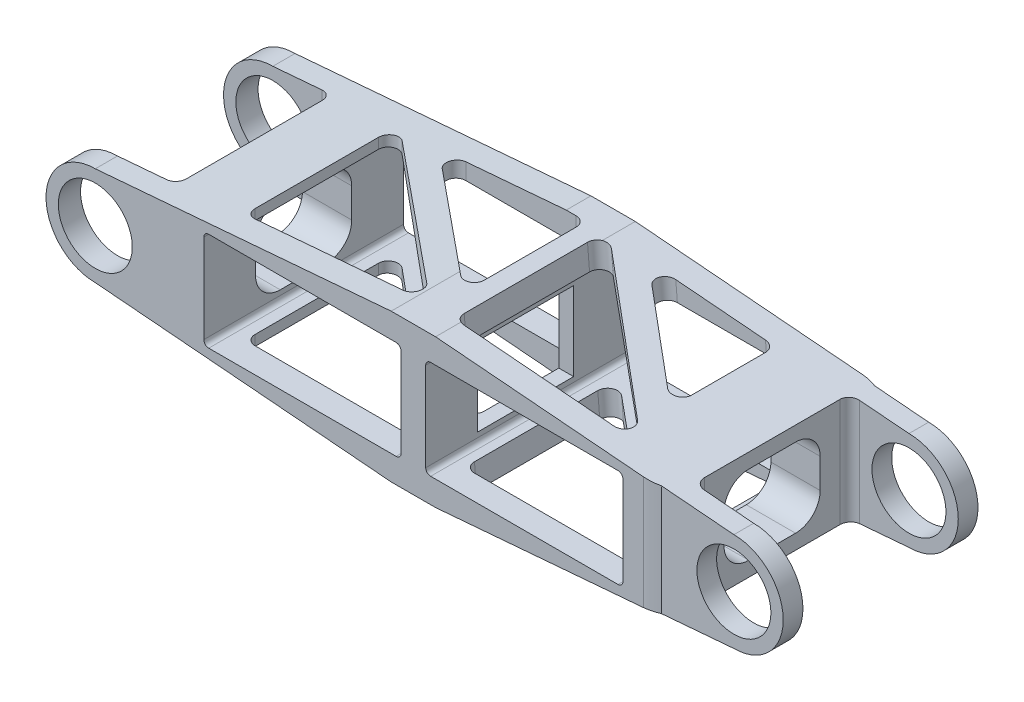
SolidWorks part; units mm, degrees
ref_plane "Plan de face" through (0, 0, 0) normal (0, 0, 1) x (1, 0, 0)
ref_plane "Plan de dessus" through (0, 0, 0) normal (0, 1, 0) x (1, 0, 0)
ref_plane "Plan de droite" through (0, 0, 0) normal (1, 0, 0) x (0, 0, -1)
sketch "Esquisse1" plane through (0, 0, 0) normal (0, 0, 1) x (1, 0, 0)
  line L1 (0, 0) -> (150, 0)
  line L2 (0, 0) -> (0, 30)
  line L3 (0, 30) -> (150, 30)
  line L4 (150, 0) -> (150, 30)
  dimension "D1" = 30
  dimension "D2" = 150
extrude "Boss.-Extru.1" add sketch "Esquisse1" along normal blind 40.5
sketch "Esquisse3" plane through (0, 0, 40.5) normal (0, 0, 1) x (1, 0, 0)
  line L0 (150, 0) -> (150, 30) construction
  arc A0 (150, 0) -> (150, 30) centre (150, 15) ccw
  circle A1 centre (150, 15) radius 7.5
  line M3 (150, 0) -> (150, 30)
  dimension "D1" = 15
extrude "Boss.-Extru.2" add sketch "Esquisse3" against normal through all contours A1 A0 M3 region at (150.3354, 3.75, 40.5)
extrude "Enlèv. mat.-Extru.2" cut sketch "Esquisse3<3>" against normal through all contours A1 M3 region at (146.8169, 15, 40.5)
sketch "Esquisse3<3>" plane through (0, 0, 40.5) normal (0, 0, 1) x (1, 0, 0) same geometry as "Esquisse3"
sketch "Esquisse4" plane through (0, 0, 0) normal (-1, 0, 0) x (0, 0, 1)
  line L0 (0, 30) -> (0, 0) construction
  line L1 (4.5, -6.4053) -> (36, -6.4053)
  line L2 (4.5, -6.4053) -> (4.5, 38.4976)
  line L3 (4.5, 38.4976) -> (36, 38.4976)
  line L4 (36, -6.4053) -> (36, 38.4976)
  line L5 (40.5, 30) -> (40.5, 0) construction
  dimension "D1" = 4.5
  dimension "D2" = 4.5
extrude "Enlèv. mat.-Extru.3" cut sketch "Esquisse4" against normal blind 50 from offset 138 offset against normal yes
sketch "Esquisse5" plane through (0, 0, 0) normal (0, 0, -1) x (-1, 0, 0)
  line L0 (-150, 5) -> (-90, 0)
  line L1 (0, 0) -> (-150, 0) construction
  line L2 (-90, 0) -> (-97.1695, -29.0949)
  line L3 (-97.1695, -29.0949) -> (-150.8097, -33.3502)
  line L4 (-150.8097, -33.3502) -> (-184.8879, -24.3272)
  line L5 (-184.8879, -24.3272) -> (-184.8879, 20.3818)
  line L6 (-184.8879, 20.3818) -> (-179.0278, 90.7023)
  line L7 (-179.0278, 90.7023) -> (-113.2138, 74.2307)
  line L8 (-113.2138, 74.2307) -> (-110.8934, 74.2182)
  line L9 (-80.3627, 70.0357) -> (-78.45, 69.7746)
  line L10 (-110.8934, 74.2182) -> (-88.7692, 44.7696)
  line L11 (-88.7692, 44.7696) -> (-90, 30)
  line L12 (-150, 30) -> (0, 30) construction
  line L13 (-90, 30) -> (-150, 25)
  arc A0 (-150, 25) -> (-150, 5) centre (-150, 15) ccw
  line M2 (0, 30) -> (-150, 30)
  arc M3 (-150, 30) -> (-150, 0) centre (-150, 15) ccw
  line M4 (-150, 0) -> (0, 0)
  dimension "D1" = 20
  dimension "D2" = 60
  dimension "D3" = 60
extrude "Enlèv. mat.-Extru.4" cut sketch "Esquisse5" against normal blind 50 contours A0 L13 L0 M2 M3 M4 region at (120.0671, 1.695, 0)
sketch "Esquisse6" plane through (0, 0, 0) normal (0, 0, -1) x (-1, 0, 0)
  line L1 (-179.8706, 2.3854) -> (-139.062, 2.3854)
  line L2 (-179.8706, 2.3854) -> (-179.8706, 33.5977)
  line L3 (-179.8706, 33.5977) -> (-139.062, 33.5977)
  line L4 (-139.062, 2.3854) -> (-139.062, 33.5977)
extrude "Enlèv. mat.-Extru.5" cut sketch "Esquisse6" against normal blind 0.5
sketch "Esquisse7" plane through (0, 0, 40.5) normal (0, 0, 1) x (1, 0, 0)
  line L1 (165.9667, 35.4579) -> (135.2799, 35.4579)
  line L2 (165.9667, 35.4579) -> (165.9667, -12.2047)
  line L3 (165.9667, -12.2047) -> (135.2799, -12.2047)
  line L4 (135.2799, 35.4579) -> (135.2799, -12.2047)
extrude "Enlèv. mat.-Extru.6" cut sketch "Esquisse7" against normal blind 0.5
sketch "Esquisse8" plane through (0, 0, 0) normal (0, 0, -1) x (-1, 0, 0)
  line L0 (0, 15) -> (-256, 15) construction
  line L1 (-127, 5) -> (-89, 5)
  line L2 (-128, 6) -> (-128, 24)
  line L3 (-127, 25) -> (-89, 25)
  line L4 (-88, 6) -> (-88, 24)
  line L5 (0, 30) -> (0, 0) construction
  arc A0 (-89, 25) -> (-88, 24) centre (-89, 24) cw
  arc A1 (-88, 6) -> (-89, 5) centre (-89, 6) cw
  arc A2 (-127, 25) -> (-128, 24) centre (-127, 24) ccw
  arc A3 (-128, 6) -> (-127, 5) centre (-127, 6) ccw
  circle A4 centre (-150, 15) radius 7.5 construction
  point P8 (-128, 15)
  point P13 (-88, 5)
  point P16 (-128, 25)
  point P19 (-128, 5)
  dimension "D3" = 1
  dimension "D1" = 20
  dimension "D2" = 40
  dimension "D4" = 22
extrude "Enlèv. mat.-Extru.7" cut sketch "Esquisse8" against normal through all
fillet "Congé1" radius 2 2 edges at (138, 15, 4.5) (138, 15, 36)
fillet "Congé2" radius 10 2 edges at (139.062, 15, 0) (135.2799, 15, 40.5)
sketch "Esquisse9" plane through (138, 0, 0) normal (1, 0, 0) x (0, 0, -1)
  line L0 (-6.5, 26) -> (-34, 26) construction
  line L1 (-10.5, 23) -> (-30, 23)
  line L2 (-10.5, 23) -> (-10.5, 7)
  line L3 (-10.5, 7) -> (-30, 7)
  line L4 (-30, 23) -> (-30, 7)
  line L5 (-6.5, 15) -> (-14.5, 15) construction
  line L6 (-6.5, 4) -> (-6.5, 26) construction
  line L7 (-20.25, 41.5871) -> (-20.25, 4.4129) construction
  point P8 (-10.5, 15)
  point P13 (-20.25, 23)
  dimension "D1" = 3
  dimension "D2" = 13.75
  dimension "D3" = 4
extrude "Enlèv. mat.-Extru.8" cut sketch "Esquisse9" against normal through all
sketch "Esquisse10" plane through (0.6207, -7.4483, 0) normal (0.083, -0.9965, 0) x (0.9965, 0.083, 0)
  line L0 (121.974, 23.5364) -> (103.974, 8.5364)
  line L1 (105.2543, 5) -> (123.2543, 5)
  line L2 (125.2543, 7) -> (125.2543, 22)
  line L3 (124.2763, 31.9636) -> (94.2763, 6.9636)
  line L4 (90.9959, 8.5) -> (90.9959, 33.5)
  line L5 (92.9959, 35.5) -> (122.9959, 35.5)
  line L6 (131.9926, 40.5) -> (89.6891, 40.5) construction
  line L8 (135.7879, 0) -> (89.6891, 0) construction
  arc A0 (94.2763, 6.9636) -> (90.9959, 8.5) centre (92.9959, 8.5) cw
  arc A1 (90.9959, 33.5) -> (92.9959, 35.5) centre (92.9959, 33.5) cw
  arc A2 (122.9959, 35.5) -> (124.2763, 31.9636) centre (122.9959, 33.5) cw
  arc A3 (105.2543, 5) -> (103.974, 8.5364) centre (105.2543, 7) cw
  arc A4 (125.2543, 22) -> (121.974, 23.5364) centre (123.2543, 22) ccw
  arc A5 (125.2543, 7) -> (123.2543, 5) centre (123.2543, 7) cw
  point P15 (0, 0)
  point P16 (125.5669, 26.3)
  point P17 (125.1675, 26.3)
  dimension "D1" = 2
  dimension "D7" = 2
  dimension "D2" = 30
  dimension "D3" = 25
  dimension "D4" = 5
  dimension "D5" = 5
  dimension "D6" = 5
  dimension "D8" = 15
extrude "Enlèv. mat.-Extru.9" cut sketch "Esquisse10" against normal through all
fillet "Congé4" radius 5 4 edges at (133, 7, 30) (133, 7, 10.5) (133, 23, 10.5) (133, 23, 30)
sketch "Esquisse11" plane through (0, 0, 0) normal (0, 0, -1) x (-1, 0, 0)
  line L0 (-88, 15) -> (-78, 15) construction
  line L1 (-82, 5) -> (-44, 5)
  line L2 (-83, 6) -> (-83, 24)
  line L3 (-82, 25) -> (-44, 25)
  line L4 (-43, 6) -> (-43, 24)
  line L5 (-88, 6) -> (-88, 24) construction
  arc A0 (-83, 24) -> (-82, 25) centre (-82, 24) cw
  arc A1 (-44, 25) -> (-43, 24) centre (-44, 24) cw
  arc A2 (-43, 6) -> (-44, 5) centre (-44, 6) cw
  arc A3 (-82, 5) -> (-83, 6) centre (-82, 6) cw
  point P8 (-83, 15)
  point P11 (-83, 25)
  point P16 (-43, 5)
  point P19 (-83, 5)
  dimension "D3" = 1
  dimension "D1" = 20
  dimension "D2" = 40
  dimension "D4" = 5
extrude "Enlèv. mat.-Extru.10" cut sketch "Esquisse11" against normal through all and the other way through all
sketch "Esquisse12" plane through (0, 0, 0) normal (0, -1, 0) x (1, 0, 0)
  line L0 (81.7501, 27.1653) -> (59.3561, 8.5036)
  line L1 (60.6245, 5) -> (83.0186, 5)
  line L2 (85, 6.9814) -> (85, 25.6431)
  line L3 (79.5697, 31.8568) -> (49.5697, 6.8568)
  line L4 (46.2893, 8.3932) -> (46.2893, 33.3932)
  line L5 (48.2893, 35.3932) -> (78.2893, 35.3932)
  line L6 (0, 0) -> (90, 0) construction
  line L7 (90, 40.5) -> (90, 0) construction
  arc A0 (49.5697, 6.8568) -> (46.2893, 8.3932) centre (48.2893, 8.3932) cw
  arc A1 (46.2893, 33.3932) -> (48.2893, 35.3932) centre (48.2893, 33.3932) cw
  arc A2 (78.2893, 35.3932) -> (79.5697, 31.8568) centre (78.2893, 33.3932) cw
  arc A3 (60.6245, 5) -> (59.3561, 8.5036) centre (60.6245, 6.9814) cw
  arc A4 (85, 25.6431) -> (81.7501, 27.1653) centre (83.0186, 25.6431) ccw
  arc A5 (85, 6.9814) -> (83.0186, 5) centre (83.0186, 6.9814) cw
  dimension "D1" = 30
  dimension "D2" = 25
  dimension "D3" = 5
  dimension "D4" = 5
  dimension "D5" = 5
extrude "Enlèv. mat.-Extru.11" cut sketch "Esquisse12" against normal through all
sketch "Esquisse13" plane through (0, 0, 0) normal (0, 0, -1) x (-1, 0, 0)
  line L0 (0, 15) -> (-36.2577, 15) construction
  line L1 (0, 30) -> (0, 0) construction
  line L2 (-43, 6) -> (-43, 24) construction
  circle A0 centre (-21, 15) radius 7.5
  point P7 (0, 0)
  dimension "D1" = 15
  dimension "D3" = 22
extrude "Enlèv. mat.-Extru.12" cut sketch "Esquisse13" against normal through all
sketch "Esquisse14" plane through (0, 0, 0) normal (0, 0, -1) x (-1, 0, 0)
  line L0 (-21, 5) -> (-81, 0)
  line L1 (0, 0) -> (-90, 0) construction
  line L2 (-81, 0) -> (-81, -20.6152)
  line L3 (-81, -20.6152) -> (7.9272, -20.6152)
  line L4 (7.9272, -20.6152) -> (9.5519, 56.9564)
  line L5 (9.5519, 56.9564) -> (-81, 56.9564)
  line L6 (-81, 56.9564) -> (-81, 30)
  line L7 (-90, 30) -> (0, 30) construction
  line L8 (-81, 30) -> (-21, 25)
  arc A0 (-21, 5) -> (-21, 25) centre (-21, 15) ccw
  point P1 (0, 0)
  dimension "D1" = 20
  dimension "D2" = 60
  dimension "D3" = 60
extrude "Enlèv. mat.-Extru.13" cut sketch "Esquisse14" against normal through all
sketch "Esquisse15" plane through (138, 0, 0) normal (1, 0, 0) x (0, 0, -1)
  line L0 (-4.5, 25.8333) -> (-4.5, 4.1667) construction
  line L1 (-4.5, 41.9079) -> (-36, 41.9079)
  line L2 (-4.5, 41.9079) -> (-4.5, -20.6366)
  line L3 (-4.5, -20.6366) -> (-36, -20.6366)
  line L4 (-36, 41.9079) -> (-36, -20.6366)
  line L5 (-36, 4.1667) -> (-36, 25.8333) construction
extrude "Enlèv. mat.-Extru.14" cut sketch "Esquisse15" against normal blind 45 from offset 105 offset against normal yes
fillet "Congé5" radius 2 2 edges at (33, 15, 4.5) (33, 15, 36)
fillet "Congé6" radius 5 4 edges at (38, 23, 30) (38, 23, 10.5) (38, 7, 10.5) (38, 7, 30)
